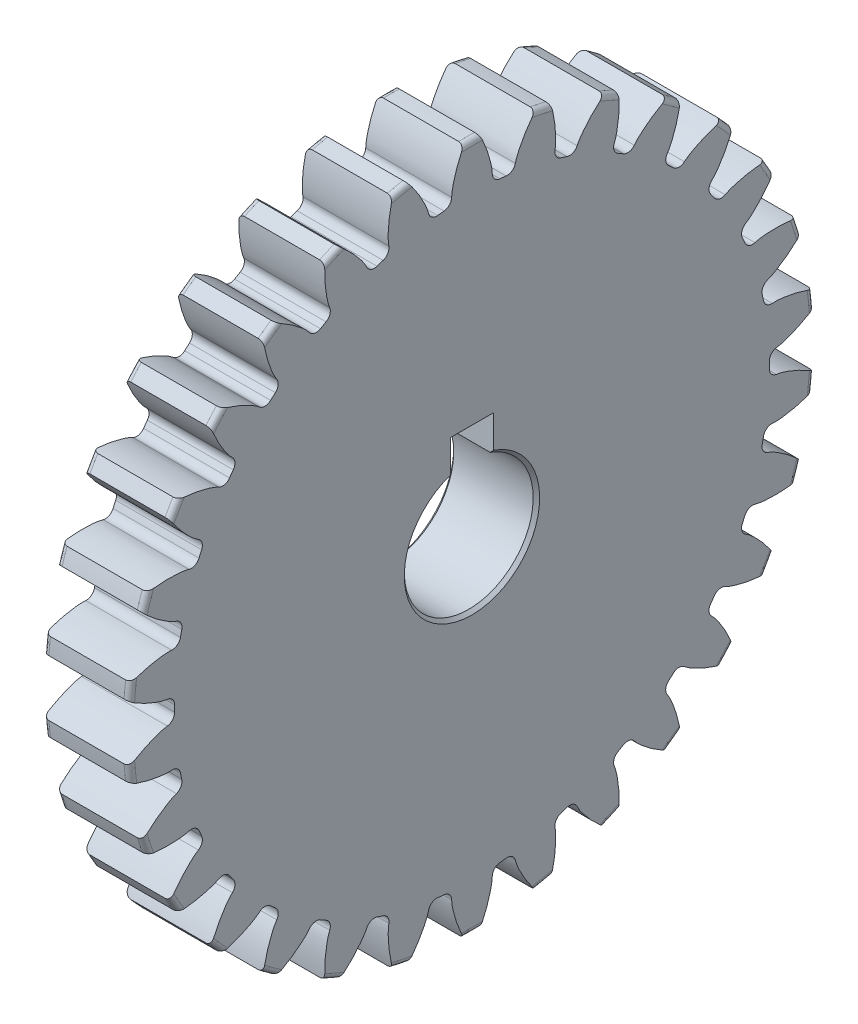
SolidWorks part; units mm, degrees
ref_plane "Front Plane" through (0, 0, 0) normal (0, 0, 1) x (1, 0, 0)
ref_plane "Top Plane" through (0, 0, 0) normal (0, 1, 0) x (1, 0, 0)
ref_plane "Right Plane" through (0, 0, 0) normal (1, 0, 0) x (0, 0, -1)
sketch "Sketch1" plane through (0, 0, 0) normal (0, 0, 1) x (1, 0, 0)
  line L0 (-4.5, 16) -> (-4.5, 0)
  line L1 (-4.5, 0) -> (4.5, 0)
  line L2 (4.5, 0) -> (4.5, 16)
  line L3 (4.5, 16) -> (-4.5, 16)
  line L4 (-4.5, 0) -> (4.5, 0) construction
revolve "Revolve1" add sketch "Sketch1" angle 360 about L4 reverse direction yes
sketch "Sketch2" plane through (-4.5, 0, 0) normal (-1, 0, 0) x (0, 0, 1)
  arc A0 (0.9541, 13.8101) -> (1.9381, 13.7067) centre (0, 0) cw
  arc A1 (2.9651, 15.7229) -> (0.3687, 15.9958) centre (0, 0) ccw
  spline S0 degree 3 poles (0.3687, 15.9958) (0.4111, 15.912) (0.4521, 15.8276) (0.4915, 15.7423) (0.5615, 15.5907) (0.6264, 15.4366) (0.6838, 15.2798) (0.7414, 15.123) (0.7918, 14.9633) (0.8344, 14.8018) (0.89, 14.5911) (0.9382, 14.3754) (0.9452, 14.1576) (0.949, 14.0418) (0.9511, 13.9259) (0.9541, 13.8101) knots -0.000282 -0.000282 -0.000282 -0.000282 0 0 0 0.000501 0.000501 0.000501 0.001002 0.001002 0.001002 0.001658 0.001658 0.001658 0.002003 0.002003 0.002003 0.002003
  spline S1 degree 3 poles (1.9381, 13.7067) (1.965, 13.8194) (1.9912, 13.9322) (2.019, 14.0447) (2.0592, 14.2078) (2.1235, 14.365) (2.1953, 14.5168) (2.2668, 14.6678) (2.3448, 14.8159) (2.4297, 14.9597) (2.5401, 15.1466) (2.6623, 15.3267) (2.7923, 15.5005) (2.8485, 15.5757) (2.9062, 15.6498) (2.9651, 15.7229) knots -0.000345 -0.000345 -0.000345 -0.000345 0 0 0 0.000504 0.000504 0.000504 0.001004 0.001004 0.001004 0.001654 0.001654 0.001654 0.001934 0.001934 0.001934 0.001934
extrude "Cut-Extrude1" cut sketch "Sketch2" against normal through all
sketch "Sketch3" plane through (-4.5, 0, 0) normal (-1, 0, 0) x (0, 0, 1)
  arc A0 (3.8045, 13.3099) -> (4.7455, 13.0042) centre (0, 0) cw
  arc A1 (6.1693, 14.7628) -> (3.6863, 15.5696) centre (0, 0) ccw
  spline S0 degree 3 poles (3.6863, 15.5696) (3.7104, 15.4788) (3.733, 15.3877) (3.7537, 15.2961) (3.7907, 15.1333) (3.8221, 14.969) (3.8457, 14.8037) (3.8694, 14.6384) (3.8856, 14.4717) (3.8937, 14.3049) (3.9042, 14.0872) (3.9065, 13.8662) (3.8681, 13.6517) (3.8477, 13.5376) (3.8257, 13.4239) (3.8045, 13.3099) knots -0.000282 -0.000282 -0.000282 -0.000282 0 0 0 0.000501 0.000501 0.000501 0.001002 0.001002 0.001002 0.001658 0.001658 0.001658 0.002003 0.002003 0.002003 0.002003
  spline S1 degree 3 poles (4.7455, 13.0042) (4.7953, 13.1088) (4.8444, 13.2138) (4.8949, 13.3181) (4.9682, 13.4692) (5.0637, 13.6096) (5.1656, 13.7432) (5.2668, 13.876) (5.374, 14.0046) (5.4869, 14.1276) (5.6337, 14.2875) (5.7907, 14.4382) (5.954, 14.5812) (6.0246, 14.6431) (6.0964, 14.7036) (6.1693, 14.7628) knots -0.000345 -0.000345 -0.000345 -0.000345 0 0 0 0.000504 0.000504 0.000504 0.001004 0.001004 0.001004 0.001654 0.001654 0.001654 0.001934 0.001934 0.001934 0.001934
extrude "Cut-Extrude2" cut sketch "Sketch3" against normal through all
sketch "Sketch4" plane through (-4.5, 0, 0) normal (-1, 0, 0) x (0, 0, 1)
  arc A0 (6.4886, 12.2281) -> (7.3455, 11.7334) centre (0, 0) cw
  arc A1 (9.1038, 13.1575) -> (6.8429, 14.4629) centre (0, 0) ccw
  spline S0 degree 3 poles (6.8429, 14.4629) (6.8476, 14.3691) (6.8507, 14.2753) (6.852, 14.1814) (6.8542, 14.0145) (6.8508, 13.8472) (6.8396, 13.6806) (6.8283, 13.514) (6.8095, 13.3476) (6.7827, 13.1828) (6.7478, 12.9677) (6.704, 12.751) (6.6219, 12.5492) (6.5782, 12.4418) (6.5331, 12.3351) (6.4886, 12.2281) knots -0.000282 -0.000282 -0.000282 -0.000282 0 0 0 0.000501 0.000501 0.000501 0.001002 0.001002 0.001002 0.001658 0.001658 0.001658 0.002003 0.002003 0.002003 0.002003
  spline S1 degree 3 poles (7.3455, 11.7334) (7.416, 11.8254) (7.4858, 11.9178) (7.5569, 12.0093) (7.66, 12.142) (7.7827, 12.2594) (7.9101, 12.3689) (8.0367, 12.4777) (8.1682, 12.5813) (8.3043, 12.6781) (8.4812, 12.8039) (8.6661, 12.9188) (8.8555, 13.0247) (8.9374, 13.0705) (9.0203, 13.1147) (9.1038, 13.1575) knots -0.000345 -0.000345 -0.000345 -0.000345 0 0 0 0.000504 0.000504 0.000504 0.001004 0.001004 0.001004 0.001654 0.001654 0.001654 0.001934 0.001934 0.001934 0.001934
extrude "Cut-Extrude3" cut sketch "Sketch4" against normal through all
sketch "Sketch5" plane through (-4.5, 0, 0) normal (-1, 0, 0) x (0, 0, 1)
  arc A0 (8.8892, 10.6118) -> (9.6245, 9.9498) centre (0, 0) cw
  arc A1 (11.6405, 10.9772) -> (9.7003, 12.7241) centre (0, 0) ccw
  spline S0 degree 3 poles (9.7003, 12.7241) (9.6854, 12.6315) (9.669, 12.539) (9.6507, 12.4469) (9.6182, 12.2831) (9.5801, 12.1203) (9.5345, 11.9597) (9.4888, 11.799) (9.4358, 11.6402) (9.3754, 11.4845) (9.2965, 11.2813) (9.2086, 11.0785) (9.0863, 10.8981) (9.0213, 10.8022) (8.9549, 10.7072) (8.8892, 10.6118) knots -0.000282 -0.000282 -0.000282 -0.000282 0 0 0 0.000501 0.000501 0.000501 0.001002 0.001002 0.001002 0.001658 0.001658 0.001658 0.002003 0.002003 0.002003 0.002003
  spline S1 degree 3 poles (9.6245, 9.9498) (9.7125, 10.0251) (9.8001, 10.101) (9.8887, 10.1757) (10.0171, 10.284) (10.1615, 10.3733) (10.3088, 10.454) (10.4554, 10.5341) (10.6055, 10.6081) (10.7588, 10.6745) (10.9579, 10.7608) (11.1627, 10.8347) (11.37, 10.8989) (11.4596, 10.9267) (11.5499, 10.9527) (11.6405, 10.9772) knots -0.000345 -0.000345 -0.000345 -0.000345 0 0 0 0.000504 0.000504 0.000504 0.001004 0.001004 0.001004 0.001654 0.001654 0.001654 0.001934 0.001934 0.001934 0.001934
extrude "Cut-Extrude4" cut sketch "Sketch5" against normal through all
sketch "Sketch6" plane through (-4.5, 0, 0) normal (-1, 0, 0) x (0, 0, 1)
  arc A0 (10.9013, 8.5317) -> (11.4829, 7.7313) centre (0, 0) cw
  arc A1 (13.6684, 8.3172) -> (12.1338, 10.4293) centre (0, 0) ccw
  spline S0 degree 3 poles (12.1338, 10.4293) (12.1, 10.3417) (12.0647, 10.2547) (12.0277, 10.1684) (11.9619, 10.015) (11.8907, 9.8636) (11.8127, 9.716) (11.7346, 9.5683) (11.6498, 9.424) (11.5582, 9.2843) (11.4389, 9.102) (11.3107, 8.9218) (11.1536, 8.7708) (11.0701, 8.6906) (10.9854, 8.6114) (10.9013, 8.5317) knots -0.000282 -0.000282 -0.000282 -0.000282 0 0 0 0.000501 0.000501 0.000501 0.001002 0.001002 0.001002 0.001658 0.001658 0.001658 0.002003 0.002003 0.002003 0.002003
  spline S1 degree 3 poles (11.4829, 7.7313) (11.5846, 7.7867) (11.6861, 7.8427) (11.7882, 7.8974) (11.9364, 7.9766) (12.0962, 8.034) (12.2571, 8.0822) (12.4171, 8.1301) (12.5793, 8.1712) (12.743, 8.2043) (12.9558, 8.2474) (13.1714, 8.2771) (13.3875, 8.2968) (13.481, 8.3053) (13.5747, 8.312) (13.6684, 8.3172) knots -0.000345 -0.000345 -0.000345 -0.000345 0 0 0 0.000504 0.000504 0.000504 0.001004 0.001004 0.001004 0.001654 0.001654 0.001654 0.001934 0.001934 0.001934 0.001934
extrude "Cut-Extrude5" cut sketch "Sketch6" against normal through all
sketch "Sketch7" plane through (-4.5, 0, 0) normal (-1, 0, 0) x (0, 0, 1)
  arc A0 (12.4369, 6.0788) -> (12.8394, 5.1749) centre (0, 0) cw
  arc A1 (15.0989, 5.2936) -> (14.0371, 7.6786) centre (0, 0) ccw
  spline S0 degree 3 poles (14.0371, 7.6786) (13.9858, 7.6) (13.9331, 7.5222) (13.879, 7.4455) (13.7827, 7.3091) (13.6816, 7.1758) (13.5746, 7.0477) (13.4675, 6.9195) (13.3545, 6.7959) (13.236, 6.6783) (13.0813, 6.5248) (12.9185, 6.3752) (12.7335, 6.2602) (12.635, 6.199) (12.5358, 6.1392) (12.4369, 6.0788) knots -0.000282 -0.000282 -0.000282 -0.000282 0 0 0 0.000501 0.000501 0.000501 0.001002 0.001002 0.001002 0.001658 0.001658 0.001658 0.002003 0.002003 0.002003 0.002003
  spline S1 degree 3 poles (12.8394, 5.1749) (12.9504, 5.2079) (13.0613, 5.2417) (13.1726, 5.2739) (13.3339, 5.3206) (13.5022, 5.3435) (13.6696, 5.3572) (13.8361, 5.3708) (14.0033, 5.3773) (14.1703, 5.3756) (14.3874, 5.3735) (14.6045, 5.3577) (14.82, 5.3321) (14.9132, 5.321) (15.0062, 5.3081) (15.0989, 5.2936) knots -0.000345 -0.000345 -0.000345 -0.000345 0 0 0 0.000504 0.000504 0.000504 0.001004 0.001004 0.001004 0.001654 0.001654 0.001654 0.001934 0.001934 0.001934 0.001934
extrude "Cut-Extrude6" cut sketch "Sketch7" against normal through all
sketch "Sketch8" plane through (-4.5, 0, 0) normal (-1, 0, 0) x (0, 0, 1)
  arc A0 (13.429, 3.3602) -> (13.6347, 2.3924) centre (0, 0) cw
  arc A1 (15.8696, 2.0387) -> (15.3268, 4.5923) centre (0, 0) ccw
  spline S0 degree 3 poles (15.3268, 4.5923) (15.2603, 4.5261) (15.1926, 4.461) (15.1237, 4.3972) (15.0012, 4.2838) (14.8746, 4.1745) (14.7433, 4.0713) (14.6119, 3.9682) (14.4757, 3.8709) (14.3352, 3.7804) (14.152, 3.6625) (13.9617, 3.55) (13.7568, 3.476) (13.6478, 3.4366) (13.5383, 3.3988) (13.429, 3.3602) knots -0.000282 -0.000282 -0.000282 -0.000282 0 0 0 0.000501 0.000501 0.000501 0.001002 0.001002 0.001002 0.001658 0.001658 0.001658 0.002003 0.002003 0.002003 0.002003
  spline S1 degree 3 poles (13.6347, 2.3924) (13.7502, 2.4016) (13.8657, 2.4115) (13.9812, 2.4199) (14.1488, 2.432) (14.3181, 2.4195) (14.4847, 2.3981) (14.6504, 2.3768) (14.8153, 2.3483) (14.9783, 2.312) (15.1902, 2.2648) (15.3993, 2.2042) (15.6047, 2.1343) (15.6936, 2.1041) (15.7819, 2.0721) (15.8696, 2.0387) knots -0.000345 -0.000345 -0.000345 -0.000345 0 0 0 0.000504 0.000504 0.000504 0.001004 0.001004 0.001004 0.001654 0.001654 0.001654 0.001934 0.001934 0.001934 0.001934
extrude "Cut-Extrude7" cut sketch "Sketch8" against normal through all
sketch "Sketch9" plane through (-4.5, 0, 0) normal (-1, 0, 0) x (0, 0, 1)
  arc A0 (13.8342, 0.4947) -> (13.8342, -0.4947) centre (0, 0) cw
  arc A1 (15.9467, -1.3054) -> (15.9467, 1.3054) centre (0, 0) ccw
  spline S0 degree 3 poles (15.9467, 1.3054) (15.8678, 1.2544) (15.7881, 1.2048) (15.7075, 1.1567) (15.564, 1.0713) (15.4175, 0.9906) (15.2676, 0.9171) (15.1176, 0.8435) (14.9641, 0.7766) (14.808, 0.7174) (14.6042, 0.6401) (14.3947, 0.5696) (14.1788, 0.5398) (14.0641, 0.524) (13.9491, 0.5097) (13.8342, 0.4947) knots -0.000282 -0.000282 -0.000282 -0.000282 0 0 0 0.000501 0.000501 0.000501 0.001002 0.001002 0.001002 0.001658 0.001658 0.001658 0.002003 0.002003 0.002003 0.002003
  spline S1 degree 3 poles (13.8342, -0.4947) (13.9491, -0.5097) (14.0641, -0.524) (14.1788, -0.5398) (14.3452, -0.5628) (14.5082, -0.6103) (14.6668, -0.6659) (14.8244, -0.7211) (14.9798, -0.7833) (15.1317, -0.8527) (15.3291, -0.9429) (15.521, -1.0457) (15.7075, -1.1567) (15.7881, -1.2048) (15.8678, -1.2544) (15.9467, -1.3054) knots -0.000345 -0.000345 -0.000345 -0.000345 0 0 0 0.000504 0.000504 0.000504 0.001004 0.001004 0.001004 0.001654 0.001654 0.001654 0.001934 0.001934 0.001934 0.001934
extrude "Cut-Extrude8" cut sketch "Sketch9" against normal through all
sketch "Sketch10" plane through (-4.5, 0, 0) normal (-1, 0, 0) x (0, 0, 1)
  arc A0 (13.6347, -2.3924) -> (13.429, -3.3602) centre (0, 0) cw
  arc A1 (15.3268, -4.5923) -> (15.8696, -2.0387) centre (0, 0) ccw
  spline S0 degree 3 poles (15.8696, -2.0387) (15.7819, -2.0721) (15.6936, -2.1041) (15.6047, -2.1343) (15.4466, -2.1881) (15.2865, -2.2365) (15.1246, -2.2773) (14.9626, -2.3181) (14.7986, -2.3516) (14.6335, -2.3771) (14.4182, -2.4103) (14.1986, -2.4357) (13.9812, -2.4199) (13.8657, -2.4115) (13.7502, -2.4016) (13.6347, -2.3924) knots -0.000282 -0.000282 -0.000282 -0.000282 0 0 0 0.000501 0.000501 0.000501 0.001002 0.001002 0.001002 0.001658 0.001658 0.001658 0.002003 0.002003 0.002003 0.002003
  spline S1 degree 3 poles (13.429, -3.3602) (13.5383, -3.3988) (13.6478, -3.4366) (13.7568, -3.476) (13.9148, -3.533) (14.0643, -3.6134) (14.2078, -3.7007) (14.3505, -3.7876) (14.4896, -3.8806) (14.6238, -3.9801) (14.7981, -4.1094) (14.9644, -4.2498) (15.1237, -4.3972) (15.1926, -4.461) (15.2603, -4.5261) (15.3268, -4.5923) knots -0.000345 -0.000345 -0.000345 -0.000345 0 0 0 0.000504 0.000504 0.000504 0.001004 0.001004 0.001004 0.001654 0.001654 0.001654 0.001934 0.001934 0.001934 0.001934
extrude "Cut-Extrude9" cut sketch "Sketch10" against normal through all
sketch "Sketch11" plane through (-4.5, 0, 0) normal (-1, 0, 0) x (0, 0, 1)
  arc A0 (12.8394, -5.1749) -> (12.4369, -6.0788) centre (0, 0) cw
  arc A1 (14.0371, -7.6786) -> (15.0989, -5.2936) centre (0, 0) ccw
  spline S0 degree 3 poles (15.0989, -5.2936) (15.0062, -5.3081) (14.9132, -5.321) (14.82, -5.3321) (14.6542, -5.3518) (14.4875, -5.3659) (14.3206, -5.3721) (14.1537, -5.3783) (13.9863, -5.377) (13.8195, -5.3676) (13.602, -5.3554) (13.3819, -5.3345) (13.1726, -5.2739) (13.0613, -5.2417) (12.9504, -5.2079) (12.8394, -5.1749) knots -0.000282 -0.000282 -0.000282 -0.000282 0 0 0 0.000501 0.000501 0.000501 0.001002 0.001002 0.001002 0.001658 0.001658 0.001658 0.002003 0.002003 0.002003 0.002003
  spline S1 degree 3 poles (12.4369, -6.0788) (12.5358, -6.1392) (12.635, -6.199) (12.7335, -6.2602) (12.8761, -6.3489) (13.0057, -6.4586) (13.1279, -6.5738) (13.2494, -6.6884) (13.3662, -6.8084) (13.4767, -6.9336) (13.6203, -7.0963) (13.7538, -7.2682) (13.879, -7.4455) (13.9331, -7.5222) (13.9858, -7.6) (14.0371, -7.6786) knots -0.000345 -0.000345 -0.000345 -0.000345 0 0 0 0.000504 0.000504 0.000504 0.001004 0.001004 0.001004 0.001654 0.001654 0.001654 0.001934 0.001934 0.001934 0.001934
extrude "Cut-Extrude10" cut sketch "Sketch11" against normal through all
sketch "Sketch12" plane through (-4.5, 0, 0) normal (-1, 0, 0) x (0, 0, 1)
  arc A0 (11.4829, -7.7313) -> (10.9013, -8.5317) centre (0, 0) cw
  arc A1 (12.1338, -10.4293) -> (13.6684, -8.3172) centre (0, 0) ccw
  spline S0 degree 3 poles (13.6684, -8.3172) (13.5747, -8.312) (13.481, -8.3053) (13.3875, -8.2968) (13.2212, -8.2816) (13.0553, -8.2607) (12.8908, -8.2321) (12.7262, -8.2035) (12.5627, -8.1674) (12.4015, -8.1235) (12.1913, -8.0663) (11.9804, -8.0002) (11.7882, -7.8974) (11.6861, -7.8427) (11.5846, -7.7867) (11.4829, -7.7313) knots -0.000282 -0.000282 -0.000282 -0.000282 0 0 0 0.000501 0.000501 0.000501 0.001002 0.001002 0.001002 0.001658 0.001658 0.001658 0.002003 0.002003 0.002003 0.002003
  spline S1 degree 3 poles (10.9013, -8.5317) (10.9854, -8.6114) (11.0701, -8.6906) (11.1536, -8.7708) (11.2747, -8.8872) (11.3787, -9.0215) (11.4743, -9.1596) (11.5693, -9.297) (11.6585, -9.4386) (11.7406, -9.5841) (11.8473, -9.7731) (11.9421, -9.969) (12.0277, -10.1684) (12.0647, -10.2547) (12.1, -10.3417) (12.1338, -10.4293) knots -0.000345 -0.000345 -0.000345 -0.000345 0 0 0 0.000504 0.000504 0.000504 0.001004 0.001004 0.001004 0.001654 0.001654 0.001654 0.001934 0.001934 0.001934 0.001934
extrude "Cut-Extrude11" cut sketch "Sketch12" against normal through all
sketch "Sketch13" plane through (-4.5, 0, 0) normal (-1, 0, 0) x (0, 0, 1)
  arc A0 (9.6245, -9.9498) -> (8.8892, -10.6118) centre (0, 0) cw
  arc A1 (9.7003, -12.7241) -> (11.6405, -10.9772) centre (0, 0) ccw
  spline S0 degree 3 poles (11.6405, -10.9772) (11.5499, -10.9527) (11.4596, -10.9267) (11.37, -10.8989) (11.2105, -10.8495) (11.0525, -10.7945) (10.8975, -10.7324) (10.7425, -10.6702) (10.5901, -10.6009) (10.4416, -10.5245) (10.2478, -10.4248) (10.0552, -10.3162) (9.8887, -10.1757) (9.8001, -10.101) (9.7125, -10.0251) (9.6245, -9.9498) knots -0.000282 -0.000282 -0.000282 -0.000282 0 0 0 0.000501 0.000501 0.000501 0.001002 0.001002 0.001002 0.001658 0.001658 0.001658 0.002003 0.002003 0.002003 0.002003
  spline S1 degree 3 poles (8.8892, -10.6118) (8.9549, -10.7072) (9.0213, -10.8022) (9.0863, -10.8981) (9.1806, -11.0372) (9.2544, -11.1901) (9.3191, -11.3451) (9.3835, -11.4992) (9.4414, -11.6563) (9.4914, -11.8156) (9.5564, -12.0227) (9.6085, -12.2341) (9.6507, -12.4469) (9.669, -12.539) (9.6854, -12.6315) (9.7003, -12.7241) knots -0.000345 -0.000345 -0.000345 -0.000345 0 0 0 0.000504 0.000504 0.000504 0.001004 0.001004 0.001004 0.001654 0.001654 0.001654 0.001934 0.001934 0.001934 0.001934
extrude "Cut-Extrude12" cut sketch "Sketch13" against normal through all
sketch "Sketch14" plane through (-4.5, 0, 0) normal (-1, 0, 0) x (0, 0, 1)
  arc A0 (7.3455, -11.7334) -> (6.4886, -12.2281) centre (0, 0) cw
  arc A1 (6.8429, -14.4629) -> (9.1038, -13.1575) centre (0, 0) ccw
  spline S0 degree 3 poles (9.1038, -13.1575) (9.0203, -13.1147) (8.9374, -13.0705) (8.8555, -13.0247) (8.7098, -12.9432) (8.5667, -12.8566) (8.428, -12.7636) (8.2893, -12.6705) (8.1546, -12.571) (8.0252, -12.4654) (7.8564, -12.3276) (7.6907, -12.1814) (7.5569, -12.0093) (7.4858, -11.9178) (7.416, -11.8254) (7.3455, -11.7334) knots -0.000282 -0.000282 -0.000282 -0.000282 0 0 0 0.000501 0.000501 0.000501 0.001002 0.001002 0.001002 0.001658 0.001658 0.001658 0.002003 0.002003 0.002003 0.002003
  spline S1 degree 3 poles (6.4886, -12.2281) (6.5331, -12.3351) (6.5782, -12.4418) (6.6219, -12.5492) (6.6852, -12.7047) (6.7256, -12.8697) (6.7567, -13.0347) (6.7877, -13.1989) (6.8116, -13.3645) (6.8274, -13.5308) (6.848, -13.7469) (6.8549, -13.9644) (6.852, -14.1814) (6.8507, -14.2753) (6.8476, -14.3691) (6.8429, -14.4629) knots -0.000345 -0.000345 -0.000345 -0.000345 0 0 0 0.000504 0.000504 0.000504 0.001004 0.001004 0.001004 0.001654 0.001654 0.001654 0.001934 0.001934 0.001934 0.001934
extrude "Cut-Extrude13" cut sketch "Sketch14" against normal through all
sketch "Sketch15" plane through (-4.5, 0, 0) normal (-1, 0, 0) x (0, 0, 1)
  arc A0 (4.7455, -13.0042) -> (3.8045, -13.3099) centre (0, 0) cw
  arc A1 (3.6863, -15.5696) -> (6.1693, -14.7628) centre (0, 0) ccw
  spline S0 degree 3 poles (6.1693, -14.7628) (6.0964, -14.7036) (6.0246, -14.6431) (5.954, -14.5812) (5.8284, -14.4712) (5.7064, -14.3568) (5.5901, -14.2369) (5.4738, -14.117) (5.3628, -13.9918) (5.2582, -13.8615) (5.1217, -13.6917) (4.9899, -13.5141) (4.8949, -13.3181) (4.8444, -13.2138) (4.7953, -13.1088) (4.7455, -13.0042) knots -0.000282 -0.000282 -0.000282 -0.000282 0 0 0 0.000501 0.000501 0.000501 0.001002 0.001002 0.001002 0.001658 0.001658 0.001658 0.002003 0.002003 0.002003 0.002003
  spline S1 degree 3 poles (3.8045, -13.3099) (3.8257, -13.4239) (3.8477, -13.5376) (3.8681, -13.6517) (3.8977, -13.8171) (3.9029, -13.9868) (3.899, -14.1547) (3.8951, -14.3217) (3.8841, -14.4887) (3.865, -14.6546) (3.8402, -14.8702) (3.8018, -15.0845) (3.7537, -15.2961) (3.733, -15.3877) (3.7104, -15.4788) (3.6863, -15.5696) knots -0.000345 -0.000345 -0.000345 -0.000345 0 0 0 0.000504 0.000504 0.000504 0.001004 0.001004 0.001004 0.001654 0.001654 0.001654 0.001934 0.001934 0.001934 0.001934
extrude "Cut-Extrude14" cut sketch "Sketch15" against normal through all
sketch "Sketch16" plane through (-4.5, 0, 0) normal (-1, 0, 0) x (0, 0, 1)
  arc A0 (1.9381, -13.7067) -> (0.9541, -13.8101) centre (0, 0) cw
  arc A1 (0.3687, -15.9958) -> (2.9651, -15.7229) centre (0, 0) ccw
  spline S0 degree 3 poles (2.9651, -15.7229) (2.9062, -15.6498) (2.8485, -15.5757) (2.7923, -15.5005) (2.6923, -15.3668) (2.5968, -15.2295) (2.5079, -15.0881) (2.4191, -14.9466) (2.3365, -14.801) (2.2613, -14.6519) (2.1631, -14.4573) (2.0712, -14.2563) (2.019, -14.0447) (1.9912, -13.9322) (1.965, -13.8194) (1.9381, -13.7067) knots -0.000282 -0.000282 -0.000282 -0.000282 0 0 0 0.000501 0.000501 0.000501 0.001002 0.001002 0.001002 0.001658 0.001658 0.001658 0.002003 0.002003 0.002003 0.002003
  spline S1 degree 3 poles (0.9541, -13.8101) (0.9511, -13.9259) (0.949, -14.0418) (0.9452, -14.1576) (0.9398, -14.3255) (0.9096, -14.4926) (0.8709, -14.656) (0.8324, -14.8186) (0.7868, -14.9796) (0.7337, -15.138) (0.6646, -15.3437) (0.5824, -15.5453) (0.4915, -15.7423) (0.4521, -15.8276) (0.4111, -15.912) (0.3687, -15.9958) knots -0.000345 -0.000345 -0.000345 -0.000345 0 0 0 0.000504 0.000504 0.000504 0.001004 0.001004 0.001004 0.001654 0.001654 0.001654 0.001934 0.001934 0.001934 0.001934
extrude "Cut-Extrude15" cut sketch "Sketch16" against normal through all
sketch "Sketch17" plane through (-4.5, 0, 0) normal (-1, 0, 0) x (0, 0, 1)
  arc A0 (-0.9541, -13.8101) -> (-1.9381, -13.7067) centre (0, 0) cw
  arc A1 (-2.9651, -15.7229) -> (-0.3687, -15.9958) centre (0, 0) ccw
  spline S0 degree 3 poles (-0.3687, -15.9958) (-0.4111, -15.912) (-0.4521, -15.8276) (-0.4915, -15.7423) (-0.5615, -15.5907) (-0.6264, -15.4366) (-0.6838, -15.2798) (-0.7414, -15.123) (-0.7918, -14.9633) (-0.8344, -14.8018) (-0.89, -14.5911) (-0.9382, -14.3754) (-0.9452, -14.1576) (-0.949, -14.0418) (-0.9511, -13.9259) (-0.9541, -13.8101) knots -0.000282 -0.000282 -0.000282 -0.000282 0 0 0 0.000501 0.000501 0.000501 0.001002 0.001002 0.001002 0.001658 0.001658 0.001658 0.002003 0.002003 0.002003 0.002003
  spline S1 degree 3 poles (-1.9381, -13.7067) (-1.965, -13.8194) (-1.9912, -13.9322) (-2.019, -14.0447) (-2.0592, -14.2078) (-2.1235, -14.365) (-2.1953, -14.5168) (-2.2668, -14.6678) (-2.3448, -14.8159) (-2.4297, -14.9597) (-2.5401, -15.1466) (-2.6623, -15.3267) (-2.7923, -15.5005) (-2.8485, -15.5757) (-2.9062, -15.6498) (-2.9651, -15.7229) knots -0.000345 -0.000345 -0.000345 -0.000345 0 0 0 0.000504 0.000504 0.000504 0.001004 0.001004 0.001004 0.001654 0.001654 0.001654 0.001934 0.001934 0.001934 0.001934
extrude "Cut-Extrude16" cut sketch "Sketch17" against normal through all
sketch "Sketch18" plane through (-4.5, 0, 0) normal (-1, 0, 0) x (0, 0, 1)
  arc A0 (-3.8045, -13.3099) -> (-4.7455, -13.0042) centre (0, 0) cw
  arc A1 (-6.1693, -14.7628) -> (-3.6863, -15.5696) centre (0, 0) ccw
  spline S0 degree 3 poles (-3.6863, -15.5696) (-3.7104, -15.4788) (-3.733, -15.3877) (-3.7537, -15.2961) (-3.7907, -15.1333) (-3.8221, -14.969) (-3.8457, -14.8037) (-3.8694, -14.6384) (-3.8856, -14.4717) (-3.8937, -14.3049) (-3.9042, -14.0872) (-3.9065, -13.8662) (-3.8681, -13.6517) (-3.8477, -13.5376) (-3.8257, -13.4239) (-3.8045, -13.3099) knots -0.000282 -0.000282 -0.000282 -0.000282 0 0 0 0.000501 0.000501 0.000501 0.001002 0.001002 0.001002 0.001658 0.001658 0.001658 0.002003 0.002003 0.002003 0.002003
  spline S1 degree 3 poles (-4.7455, -13.0042) (-4.7953, -13.1088) (-4.8444, -13.2138) (-4.8949, -13.3181) (-4.9682, -13.4692) (-5.0637, -13.6096) (-5.1656, -13.7432) (-5.2668, -13.876) (-5.374, -14.0046) (-5.4869, -14.1276) (-5.6337, -14.2875) (-5.7907, -14.4382) (-5.954, -14.5812) (-6.0246, -14.6431) (-6.0964, -14.7036) (-6.1693, -14.7628) knots -0.000345 -0.000345 -0.000345 -0.000345 0 0 0 0.000504 0.000504 0.000504 0.001004 0.001004 0.001004 0.001654 0.001654 0.001654 0.001934 0.001934 0.001934 0.001934
extrude "Cut-Extrude17" cut sketch "Sketch18" against normal through all
sketch "Sketch19" plane through (-4.5, 0, 0) normal (-1, 0, 0) x (0, 0, 1)
  arc A0 (-6.4886, -12.2281) -> (-7.3455, -11.7334) centre (0, 0) cw
  arc A1 (-9.1038, -13.1575) -> (-6.8429, -14.4629) centre (0, 0) ccw
  spline S0 degree 3 poles (-6.8429, -14.4629) (-6.8476, -14.3691) (-6.8507, -14.2753) (-6.852, -14.1814) (-6.8542, -14.0145) (-6.8508, -13.8472) (-6.8396, -13.6806) (-6.8283, -13.514) (-6.8095, -13.3476) (-6.7827, -13.1828) (-6.7478, -12.9677) (-6.704, -12.751) (-6.6219, -12.5492) (-6.5782, -12.4418) (-6.5331, -12.3351) (-6.4886, -12.2281) knots -0.000282 -0.000282 -0.000282 -0.000282 0 0 0 0.000501 0.000501 0.000501 0.001002 0.001002 0.001002 0.001658 0.001658 0.001658 0.002003 0.002003 0.002003 0.002003
  spline S1 degree 3 poles (-7.3455, -11.7334) (-7.416, -11.8254) (-7.4858, -11.9178) (-7.5569, -12.0093) (-7.66, -12.142) (-7.7827, -12.2594) (-7.9101, -12.3689) (-8.0367, -12.4777) (-8.1682, -12.5813) (-8.3043, -12.6781) (-8.4812, -12.8039) (-8.6661, -12.9188) (-8.8555, -13.0247) (-8.9374, -13.0705) (-9.0203, -13.1147) (-9.1038, -13.1575) knots -0.000345 -0.000345 -0.000345 -0.000345 0 0 0 0.000504 0.000504 0.000504 0.001004 0.001004 0.001004 0.001654 0.001654 0.001654 0.001934 0.001934 0.001934 0.001934
extrude "Cut-Extrude18" cut sketch "Sketch19" against normal through all
sketch "Sketch20" plane through (-4.5, 0, 0) normal (-1, 0, 0) x (0, 0, 1)
  arc A0 (-8.8892, -10.6118) -> (-9.6245, -9.9498) centre (0, 0) cw
  arc A1 (-11.6405, -10.9772) -> (-9.7003, -12.7241) centre (0, 0) ccw
  spline S0 degree 3 poles (-9.7003, -12.7241) (-9.6854, -12.6315) (-9.669, -12.539) (-9.6507, -12.4469) (-9.6182, -12.2831) (-9.5801, -12.1203) (-9.5345, -11.9597) (-9.4888, -11.799) (-9.4358, -11.6402) (-9.3754, -11.4845) (-9.2965, -11.2813) (-9.2086, -11.0785) (-9.0863, -10.8981) (-9.0213, -10.8022) (-8.9549, -10.7072) (-8.8892, -10.6118) knots -0.000282 -0.000282 -0.000282 -0.000282 0 0 0 0.000501 0.000501 0.000501 0.001002 0.001002 0.001002 0.001658 0.001658 0.001658 0.002003 0.002003 0.002003 0.002003
  spline S1 degree 3 poles (-9.6245, -9.9498) (-9.7125, -10.0251) (-9.8001, -10.101) (-9.8887, -10.1757) (-10.0171, -10.284) (-10.1615, -10.3733) (-10.3088, -10.454) (-10.4554, -10.5341) (-10.6055, -10.6081) (-10.7588, -10.6745) (-10.9579, -10.7608) (-11.1627, -10.8347) (-11.37, -10.8989) (-11.4596, -10.9267) (-11.5499, -10.9527) (-11.6405, -10.9772) knots -0.000345 -0.000345 -0.000345 -0.000345 0 0 0 0.000504 0.000504 0.000504 0.001004 0.001004 0.001004 0.001654 0.001654 0.001654 0.001934 0.001934 0.001934 0.001934
extrude "Cut-Extrude19" cut sketch "Sketch20" against normal through all
sketch "Sketch21" plane through (-4.5, 0, 0) normal (-1, 0, 0) x (0, 0, 1)
  arc A0 (-10.9013, -8.5317) -> (-11.4829, -7.7313) centre (0, 0) cw
  arc A1 (-13.6684, -8.3172) -> (-12.1338, -10.4293) centre (0, 0) ccw
  spline S0 degree 3 poles (-12.1338, -10.4293) (-12.1, -10.3417) (-12.0647, -10.2547) (-12.0277, -10.1684) (-11.9619, -10.015) (-11.8907, -9.8636) (-11.8127, -9.716) (-11.7346, -9.5683) (-11.6498, -9.424) (-11.5582, -9.2843) (-11.4389, -9.102) (-11.3107, -8.9218) (-11.1536, -8.7708) (-11.0701, -8.6906) (-10.9854, -8.6114) (-10.9013, -8.5317) knots -0.000282 -0.000282 -0.000282 -0.000282 0 0 0 0.000501 0.000501 0.000501 0.001002 0.001002 0.001002 0.001658 0.001658 0.001658 0.002003 0.002003 0.002003 0.002003
  spline S1 degree 3 poles (-11.4829, -7.7313) (-11.5846, -7.7867) (-11.6861, -7.8427) (-11.7882, -7.8974) (-11.9364, -7.9766) (-12.0962, -8.034) (-12.2571, -8.0822) (-12.4171, -8.1301) (-12.5793, -8.1712) (-12.743, -8.2043) (-12.9558, -8.2474) (-13.1714, -8.2771) (-13.3875, -8.2968) (-13.481, -8.3053) (-13.5747, -8.312) (-13.6684, -8.3172) knots -0.000345 -0.000345 -0.000345 -0.000345 0 0 0 0.000504 0.000504 0.000504 0.001004 0.001004 0.001004 0.001654 0.001654 0.001654 0.001934 0.001934 0.001934 0.001934
extrude "Cut-Extrude20" cut sketch "Sketch21" against normal through all
sketch "Sketch22" plane through (-4.5, 0, 0) normal (-1, 0, 0) x (0, 0, 1)
  arc A0 (-12.4369, -6.0788) -> (-12.8394, -5.1749) centre (0, 0) cw
  arc A1 (-15.0989, -5.2936) -> (-14.0371, -7.6786) centre (0, 0) ccw
  spline S0 degree 3 poles (-14.0371, -7.6786) (-13.9858, -7.6) (-13.9331, -7.5222) (-13.879, -7.4455) (-13.7827, -7.3091) (-13.6816, -7.1758) (-13.5746, -7.0477) (-13.4675, -6.9195) (-13.3545, -6.7959) (-13.236, -6.6783) (-13.0813, -6.5248) (-12.9185, -6.3752) (-12.7335, -6.2602) (-12.635, -6.199) (-12.5358, -6.1392) (-12.4369, -6.0788) knots -0.000282 -0.000282 -0.000282 -0.000282 0 0 0 0.000501 0.000501 0.000501 0.001002 0.001002 0.001002 0.001658 0.001658 0.001658 0.002003 0.002003 0.002003 0.002003
  spline S1 degree 3 poles (-12.8394, -5.1749) (-12.9504, -5.2079) (-13.0613, -5.2417) (-13.1726, -5.2739) (-13.3339, -5.3206) (-13.5022, -5.3435) (-13.6696, -5.3572) (-13.8361, -5.3708) (-14.0033, -5.3773) (-14.1703, -5.3756) (-14.3874, -5.3735) (-14.6045, -5.3577) (-14.82, -5.3321) (-14.9132, -5.321) (-15.0062, -5.3081) (-15.0989, -5.2936) knots -0.000345 -0.000345 -0.000345 -0.000345 0 0 0 0.000504 0.000504 0.000504 0.001004 0.001004 0.001004 0.001654 0.001654 0.001654 0.001934 0.001934 0.001934 0.001934
extrude "Cut-Extrude21" cut sketch "Sketch22" against normal through all
sketch "Sketch23" plane through (-4.5, 0, 0) normal (-1, 0, 0) x (0, 0, 1)
  arc A0 (-13.429, -3.3602) -> (-13.6347, -2.3924) centre (0, 0) cw
  arc A1 (-15.8696, -2.0387) -> (-15.3268, -4.5923) centre (0, 0) ccw
  spline S0 degree 3 poles (-15.3268, -4.5923) (-15.2603, -4.5261) (-15.1926, -4.461) (-15.1237, -4.3972) (-15.0012, -4.2838) (-14.8746, -4.1745) (-14.7433, -4.0713) (-14.6119, -3.9682) (-14.4757, -3.8709) (-14.3352, -3.7804) (-14.152, -3.6625) (-13.9617, -3.55) (-13.7568, -3.476) (-13.6478, -3.4366) (-13.5383, -3.3988) (-13.429, -3.3602) knots -0.000282 -0.000282 -0.000282 -0.000282 0 0 0 0.000501 0.000501 0.000501 0.001002 0.001002 0.001002 0.001658 0.001658 0.001658 0.002003 0.002003 0.002003 0.002003
  spline S1 degree 3 poles (-13.6347, -2.3924) (-13.7502, -2.4016) (-13.8657, -2.4115) (-13.9812, -2.4199) (-14.1488, -2.432) (-14.3181, -2.4195) (-14.4847, -2.3981) (-14.6504, -2.3768) (-14.8153, -2.3483) (-14.9783, -2.312) (-15.1902, -2.2648) (-15.3993, -2.2042) (-15.6047, -2.1343) (-15.6936, -2.1041) (-15.7819, -2.0721) (-15.8696, -2.0387) knots -0.000345 -0.000345 -0.000345 -0.000345 0 0 0 0.000504 0.000504 0.000504 0.001004 0.001004 0.001004 0.001654 0.001654 0.001654 0.001934 0.001934 0.001934 0.001934
extrude "Cut-Extrude22" cut sketch "Sketch23" against normal through all
sketch "Sketch24" plane through (-4.5, 0, 0) normal (-1, 0, 0) x (0, 0, 1)
  arc A0 (-15.9467, 1.3054) -> (-15.9467, -1.3054) centre (0, 0) ccw
  arc A1 (-13.8342, -0.4947) -> (-13.8342, 0.4947) centre (0, 0) cw
  spline S0 degree 3 poles (-15.9467, -1.3054) (-15.8678, -1.2544) (-15.7881, -1.2048) (-15.7075, -1.1567) (-15.564, -1.0713) (-15.4175, -0.9906) (-15.2676, -0.9171) (-15.1176, -0.8435) (-14.9641, -0.7766) (-14.808, -0.7174) (-14.6042, -0.6401) (-14.3947, -0.5696) (-14.1788, -0.5398) (-14.0641, -0.524) (-13.9491, -0.5097) (-13.8342, -0.4947) knots -0.000282 -0.000282 -0.000282 -0.000282 0 0 0 0.000501 0.000501 0.000501 0.001002 0.001002 0.001002 0.001658 0.001658 0.001658 0.002003 0.002003 0.002003 0.002003
  spline S1 degree 3 poles (-13.8342, 0.4947) (-13.9491, 0.5097) (-14.0641, 0.524) (-14.1788, 0.5398) (-14.3452, 0.5628) (-14.5082, 0.6103) (-14.6668, 0.6659) (-14.8244, 0.7211) (-14.9798, 0.7833) (-15.1317, 0.8527) (-15.3291, 0.9429) (-15.521, 1.0457) (-15.7075, 1.1567) (-15.7881, 1.2048) (-15.8678, 1.2544) (-15.9467, 1.3054) knots -0.000345 -0.000345 -0.000345 -0.000345 0 0 0 0.000504 0.000504 0.000504 0.001004 0.001004 0.001004 0.001654 0.001654 0.001654 0.001934 0.001934 0.001934 0.001934
extrude "Cut-Extrude23" cut sketch "Sketch24" against normal through all
sketch "Sketch25" plane through (-4.5, 0, 0) normal (-1, 0, 0) x (0, 0, 1)
  arc A0 (-15.3268, 4.5923) -> (-15.8696, 2.0387) centre (0, 0) ccw
  arc A1 (-13.6347, 2.3924) -> (-13.429, 3.3602) centre (0, 0) cw
  spline S0 degree 3 poles (-15.8696, 2.0387) (-15.7819, 2.0721) (-15.6936, 2.1041) (-15.6047, 2.1343) (-15.4466, 2.1881) (-15.2865, 2.2365) (-15.1246, 2.2773) (-14.9626, 2.3181) (-14.7986, 2.3516) (-14.6335, 2.3771) (-14.4182, 2.4103) (-14.1986, 2.4357) (-13.9812, 2.4199) (-13.8657, 2.4115) (-13.7502, 2.4016) (-13.6347, 2.3924) knots -0.000282 -0.000282 -0.000282 -0.000282 0 0 0 0.000501 0.000501 0.000501 0.001002 0.001002 0.001002 0.001658 0.001658 0.001658 0.002003 0.002003 0.002003 0.002003
  spline S1 degree 3 poles (-13.429, 3.3602) (-13.5383, 3.3988) (-13.6478, 3.4366) (-13.7568, 3.476) (-13.9148, 3.533) (-14.0643, 3.6134) (-14.2078, 3.7007) (-14.3505, 3.7876) (-14.4896, 3.8806) (-14.6238, 3.9801) (-14.7981, 4.1094) (-14.9644, 4.2498) (-15.1237, 4.3972) (-15.1926, 4.461) (-15.2603, 4.5261) (-15.3268, 4.5923) knots -0.000345 -0.000345 -0.000345 -0.000345 0 0 0 0.000504 0.000504 0.000504 0.001004 0.001004 0.001004 0.001654 0.001654 0.001654 0.001934 0.001934 0.001934 0.001934
extrude "Cut-Extrude24" cut sketch "Sketch25" against normal through all
sketch "Sketch26" plane through (-4.5, 0, 0) normal (-1, 0, 0) x (0, 0, 1)
  arc A0 (-14.0371, 7.6786) -> (-15.0989, 5.2936) centre (0, 0) ccw
  arc A1 (-12.8394, 5.1749) -> (-12.4369, 6.0788) centre (0, 0) cw
  spline S0 degree 3 poles (-15.0989, 5.2936) (-15.0062, 5.3081) (-14.9132, 5.321) (-14.82, 5.3321) (-14.6542, 5.3518) (-14.4875, 5.3659) (-14.3206, 5.3721) (-14.1537, 5.3783) (-13.9863, 5.377) (-13.8195, 5.3676) (-13.602, 5.3554) (-13.3819, 5.3345) (-13.1726, 5.2739) (-13.0613, 5.2417) (-12.9504, 5.2079) (-12.8394, 5.1749) knots -0.000282 -0.000282 -0.000282 -0.000282 0 0 0 0.000501 0.000501 0.000501 0.001002 0.001002 0.001002 0.001658 0.001658 0.001658 0.002003 0.002003 0.002003 0.002003
  spline S1 degree 3 poles (-12.4369, 6.0788) (-12.5358, 6.1392) (-12.635, 6.199) (-12.7335, 6.2602) (-12.8761, 6.3489) (-13.0057, 6.4586) (-13.1279, 6.5738) (-13.2494, 6.6884) (-13.3662, 6.8084) (-13.4767, 6.9336) (-13.6203, 7.0963) (-13.7538, 7.2682) (-13.879, 7.4455) (-13.9331, 7.5222) (-13.9858, 7.6) (-14.0371, 7.6786) knots -0.000345 -0.000345 -0.000345 -0.000345 0 0 0 0.000504 0.000504 0.000504 0.001004 0.001004 0.001004 0.001654 0.001654 0.001654 0.001934 0.001934 0.001934 0.001934
extrude "Cut-Extrude25" cut sketch "Sketch26" against normal through all
sketch "Sketch27" plane through (-4.5, 0, 0) normal (-1, 0, 0) x (0, 0, 1)
  arc A0 (-12.1338, 10.4293) -> (-13.6684, 8.3172) centre (0, 0) ccw
  arc A1 (-11.4829, 7.7313) -> (-10.9013, 8.5317) centre (0, 0) cw
  spline S0 degree 3 poles (-13.6684, 8.3172) (-13.5747, 8.312) (-13.481, 8.3053) (-13.3875, 8.2968) (-13.2212, 8.2816) (-13.0553, 8.2607) (-12.8908, 8.2321) (-12.7262, 8.2035) (-12.5627, 8.1674) (-12.4015, 8.1235) (-12.1913, 8.0663) (-11.9804, 8.0002) (-11.7882, 7.8974) (-11.6861, 7.8427) (-11.5846, 7.7867) (-11.4829, 7.7313) knots -0.000282 -0.000282 -0.000282 -0.000282 0 0 0 0.000501 0.000501 0.000501 0.001002 0.001002 0.001002 0.001658 0.001658 0.001658 0.002003 0.002003 0.002003 0.002003
  spline S1 degree 3 poles (-10.9013, 8.5317) (-10.9854, 8.6114) (-11.0701, 8.6906) (-11.1536, 8.7708) (-11.2747, 8.8872) (-11.3787, 9.0215) (-11.4743, 9.1596) (-11.5693, 9.297) (-11.6585, 9.4386) (-11.7406, 9.5841) (-11.8473, 9.7731) (-11.9421, 9.969) (-12.0277, 10.1684) (-12.0647, 10.2547) (-12.1, 10.3417) (-12.1338, 10.4293) knots -0.000345 -0.000345 -0.000345 -0.000345 0 0 0 0.000504 0.000504 0.000504 0.001004 0.001004 0.001004 0.001654 0.001654 0.001654 0.001934 0.001934 0.001934 0.001934
extrude "Cut-Extrude26" cut sketch "Sketch27" against normal through all
sketch "Sketch28" plane through (-4.5, 0, 0) normal (-1, 0, 0) x (0, 0, 1)
  arc A0 (-9.7003, 12.7241) -> (-11.6405, 10.9772) centre (0, 0) ccw
  arc A1 (-9.6245, 9.9498) -> (-8.8892, 10.6118) centre (0, 0) cw
  spline S0 degree 3 poles (-11.6405, 10.9772) (-11.5499, 10.9527) (-11.4596, 10.9267) (-11.37, 10.8989) (-11.2105, 10.8495) (-11.0525, 10.7945) (-10.8975, 10.7324) (-10.7425, 10.6702) (-10.5901, 10.6009) (-10.4416, 10.5245) (-10.2478, 10.4248) (-10.0552, 10.3162) (-9.8887, 10.1757) (-9.8001, 10.101) (-9.7125, 10.0251) (-9.6245, 9.9498) knots -0.000282 -0.000282 -0.000282 -0.000282 0 0 0 0.000501 0.000501 0.000501 0.001002 0.001002 0.001002 0.001658 0.001658 0.001658 0.002003 0.002003 0.002003 0.002003
  spline S1 degree 3 poles (-8.8892, 10.6118) (-8.9549, 10.7072) (-9.0213, 10.8022) (-9.0863, 10.8981) (-9.1806, 11.0372) (-9.2544, 11.1901) (-9.3191, 11.3451) (-9.3835, 11.4992) (-9.4414, 11.6563) (-9.4914, 11.8156) (-9.5564, 12.0227) (-9.6085, 12.2341) (-9.6507, 12.4469) (-9.669, 12.539) (-9.6854, 12.6315) (-9.7003, 12.7241) knots -0.000345 -0.000345 -0.000345 -0.000345 0 0 0 0.000504 0.000504 0.000504 0.001004 0.001004 0.001004 0.001654 0.001654 0.001654 0.001934 0.001934 0.001934 0.001934
extrude "Cut-Extrude27" cut sketch "Sketch28" against normal through all
sketch "Sketch29" plane through (-4.5, 0, 0) normal (-1, 0, 0) x (0, 0, 1)
  arc A0 (-6.8429, 14.4629) -> (-9.1038, 13.1575) centre (0, 0) ccw
  arc A1 (-7.3455, 11.7334) -> (-6.4886, 12.2281) centre (0, 0) cw
  spline S0 degree 3 poles (-9.1038, 13.1575) (-9.0203, 13.1147) (-8.9374, 13.0705) (-8.8555, 13.0247) (-8.7098, 12.9432) (-8.5667, 12.8566) (-8.428, 12.7636) (-8.2893, 12.6705) (-8.1546, 12.571) (-8.0252, 12.4654) (-7.8564, 12.3276) (-7.6907, 12.1814) (-7.5569, 12.0093) (-7.4858, 11.9178) (-7.416, 11.8254) (-7.3455, 11.7334) knots -0.000282 -0.000282 -0.000282 -0.000282 0 0 0 0.000501 0.000501 0.000501 0.001002 0.001002 0.001002 0.001658 0.001658 0.001658 0.002003 0.002003 0.002003 0.002003
  spline S1 degree 3 poles (-6.4886, 12.2281) (-6.5331, 12.3351) (-6.5782, 12.4418) (-6.6219, 12.5492) (-6.6852, 12.7047) (-6.7256, 12.8697) (-6.7567, 13.0347) (-6.7877, 13.1989) (-6.8116, 13.3645) (-6.8274, 13.5308) (-6.848, 13.7469) (-6.8549, 13.9644) (-6.852, 14.1814) (-6.8507, 14.2753) (-6.8476, 14.3691) (-6.8429, 14.4629) knots -0.000345 -0.000345 -0.000345 -0.000345 0 0 0 0.000504 0.000504 0.000504 0.001004 0.001004 0.001004 0.001654 0.001654 0.001654 0.001934 0.001934 0.001934 0.001934
extrude "Cut-Extrude28" cut sketch "Sketch29" against normal through all
sketch "Sketch30" plane through (-4.5, 0, 0) normal (-1, 0, 0) x (0, 0, 1)
  arc A0 (-3.6863, 15.5696) -> (-6.1693, 14.7628) centre (0, 0) ccw
  arc A1 (-4.7455, 13.0042) -> (-3.8045, 13.3099) centre (0, 0) cw
  spline S0 degree 3 poles (-6.1693, 14.7628) (-6.0964, 14.7036) (-6.0246, 14.6431) (-5.954, 14.5812) (-5.8284, 14.4712) (-5.7064, 14.3568) (-5.5901, 14.2369) (-5.4738, 14.117) (-5.3628, 13.9918) (-5.2582, 13.8615) (-5.1217, 13.6917) (-4.9899, 13.5141) (-4.8949, 13.3181) (-4.8444, 13.2138) (-4.7953, 13.1088) (-4.7455, 13.0042) knots -0.000282 -0.000282 -0.000282 -0.000282 0 0 0 0.000501 0.000501 0.000501 0.001002 0.001002 0.001002 0.001658 0.001658 0.001658 0.002003 0.002003 0.002003 0.002003
  spline S1 degree 3 poles (-3.8045, 13.3099) (-3.8257, 13.4239) (-3.8477, 13.5376) (-3.8681, 13.6517) (-3.8977, 13.8171) (-3.9029, 13.9868) (-3.899, 14.1547) (-3.8951, 14.3217) (-3.8841, 14.4887) (-3.865, 14.6546) (-3.8402, 14.8702) (-3.8018, 15.0845) (-3.7537, 15.2961) (-3.733, 15.3877) (-3.7104, 15.4788) (-3.6863, 15.5696) knots -0.000345 -0.000345 -0.000345 -0.000345 0 0 0 0.000504 0.000504 0.000504 0.001004 0.001004 0.001004 0.001654 0.001654 0.001654 0.001934 0.001934 0.001934 0.001934
extrude "Cut-Extrude29" cut sketch "Sketch30" against normal through all
sketch "Sketch31" plane through (-4.5, 0, 0) normal (-1, 0, 0) x (0, 0, 1)
  arc A0 (-0.3687, 15.9958) -> (-2.9651, 15.7229) centre (0, 0) ccw
  arc A1 (-1.9381, 13.7067) -> (-0.9541, 13.8101) centre (0, 0) cw
  spline S0 degree 3 poles (-2.9651, 15.7229) (-2.9062, 15.6498) (-2.8485, 15.5757) (-2.7923, 15.5005) (-2.6923, 15.3668) (-2.5968, 15.2295) (-2.5079, 15.0881) (-2.4191, 14.9466) (-2.3365, 14.801) (-2.2613, 14.6519) (-2.1631, 14.4573) (-2.0712, 14.2563) (-2.019, 14.0447) (-1.9912, 13.9322) (-1.965, 13.8194) (-1.9381, 13.7067) knots -0.000282 -0.000282 -0.000282 -0.000282 0 0 0 0.000501 0.000501 0.000501 0.001002 0.001002 0.001002 0.001658 0.001658 0.001658 0.002003 0.002003 0.002003 0.002003
  spline S1 degree 3 poles (-0.9541, 13.8101) (-0.9511, 13.9259) (-0.949, 14.0418) (-0.9452, 14.1576) (-0.9398, 14.3255) (-0.9096, 14.4926) (-0.8709, 14.656) (-0.8324, 14.8186) (-0.7868, 14.9796) (-0.7337, 15.138) (-0.6646, 15.3437) (-0.5824, 15.5453) (-0.4915, 15.7423) (-0.4521, 15.8276) (-0.4111, 15.912) (-0.3687, 15.9958) knots -0.000345 -0.000345 -0.000345 -0.000345 0 0 0 0.000504 0.000504 0.000504 0.001004 0.001004 0.001004 0.001654 0.001654 0.001654 0.001934 0.001934 0.001934 0.001934
extrude "Cut-Extrude30" cut sketch "Sketch31" against normal through all
ref_plane "Plane4" through (0, 0, 0) normal (0, 0, -1) x (-1, 0, 0)
fillet "Fillet2" radius 0.39 60 edges at (0, -0.4947, -13.8342) (0, 9.9498, -9.6245) (0, 5.1749, -12.8394) (0, -13.8101, 0.9541) (0, 13.0042, -4.7455) (0, -13.7067, 1.9381) (0, 2.3924, -13.6347) (0, -13.8101, -0.9541) (0, 7.7313, -11.4829) (0, -13.7067, -1.9381) (0, 11.7334, -7.3455) (0, -13.3099, 3.8045) (0, 13.8101, -0.9541) (0, -13.0042, 4.7455) (0, 2.3924, 13.6347) (0, -13.3099, -3.8045) (0, 5.1749, 12.8394) (0, -13.0042, -4.7455) (0, 7.7313, 11.4829) (0, -12.2281, 6.4886) (0, 9.9498, 9.6245) (0, -11.7334, 7.3455) (0, 11.7334, 7.3455) (0, -12.2281, -6.4886) (0, 13.0042, 4.7455) (0, -11.7334, -7.3455) (0, 13.7067, 1.9381) (0, -10.6118, 8.8892) (0, 0.4947, 13.8342) (0, -9.9498, 9.6245) (0, 0.4947, -13.8342) (0, -10.6118, -8.8892) (0, 3.3602, 13.429) (0, -9.9498, -9.6245) (0, 3.3602, -13.429) (0, -8.5317, 10.9013) (0, 6.0788, 12.4369) (0, -7.7313, 11.4829) (0, 6.0788, -12.4369) (0, -8.5317, -10.9013) (0, 8.5317, 10.9013) (0, -7.7313, -11.4829) (0, 8.5317, -10.9013) (0, -6.0788, 12.4369) (0, 10.6118, 8.8892) (0, -5.1749, 12.8394) (0, 10.6118, -8.8892) (0, -6.0788, -12.4369) (0, 12.2281, 6.4886) (0, -5.1749, -12.8394) (0, 12.2281, -6.4886) (0, -3.3602, 13.429) (0, 13.3099, 3.8045) (0, -2.3924, 13.6347) (0, 13.3099, -3.8045) (0, -3.3602, -13.429) (0, 13.8101, 0.9541) (0, -2.3924, -13.6347) (0, -0.4947, 13.8342) (0, 13.7067, -1.9381) tangent propagation no
sketch "Sketch40" plane through (0, 0, 0) normal (0, 1, 0) x (1, 0, 0)
  line L0 (-4.5, 15.0989) -> (-4.5, 13.1726) construction
  line L1 (-8.4464, 17.2217) -> (-2.5, 17.2217)
  line L2 (-8.4464, 17.2217) -> (-8.4464, -17.5419)
  line L3 (-8.4464, -17.5419) -> (-2.5, -17.5419)
  line L4 (-2.5, 17.2217) -> (-2.5, -17.5419)
  line L5 (2.5, -17.5419) -> (8.7666, -17.5419)
  line L6 (2.5, -17.5419) -> (2.5, 17.2217)
  line L7 (2.5, 17.2217) -> (8.7666, 17.2217)
  line L8 (8.7666, -17.5419) -> (8.7666, 17.2217)
  line L9 (4.5, 13.1726) -> (4.5, 15.0989) construction
  dimension "D1" = 2
  dimension "D2" = 2
extrude "Cut-Extrude31" cut sketch "Sketch40" against normal mid plane 40
hole_wizard "Ø4.0 (4) Diameter Hole1" positions "Sketch42" profile "Sketch41" hole size "Ø4.0" standard "ANSI Metric" end condition through all
sketch "Sketch42" plane through (-2.5, 0, 0) normal (-1, 0, 0) x (0, 0, 1)
  point P0 (0, 0)
sketch "Sketch41" plane through (-2.5, 0, 0) normal (0, 1, 0) x (0, 0, 1)
  line L0 (0, 0) -> (0, 5)
  line L1 (0, 5) -> (3, 5)
  line L2 (3, 5) -> (3, 0)
  line L5 (3, 0) -> (0, 0)
  line L11 (0, -6.35) -> (0, 107.95) construction
  dimension "Thru Hole Dia." = 6
  dimension "Thru Hole Depth" = 5
sketch "Sketch43" plane through (2.5, 0, 0) normal (1, 0, 0) x (0, 0, -1)
  line L0 (-1, 2.8284) -> (-1, 4.5)
  line L1 (-1, 4.5) -> (1, 4.5)
  line L2 (1, 4.5) -> (1, 2.8284)
  arc A0 (1, 2.8284) -> (-1, 2.8284) centre (0, 0) ccw
  dimension "D1" = 2
extrude "Cut-Extrude32" cut sketch "Sketch43" against normal through all
sketch "Sketch44" plane through (0, 0, 0) normal (0, 1, 0) x (1, 0, 0)
  line L0 (-2.5, 15.0989) -> (-2.5, 13.1726) construction
  line L1 (-4.2364, 16.7956) -> (-2, 16.7956)
  line L2 (-4.2364, 16.7956) -> (-4.2364, -16.7509)
  line L3 (-4.2364, -16.7509) -> (-2, -16.7509)
  line L4 (-2, 16.7956) -> (-2, -16.7509)
  line L5 (2, 16.7956) -> (6.2045, 16.7956)
  line L6 (2, 16.7956) -> (2, -16.7509)
  line L7 (2, -16.7509) -> (6.2045, -16.7509)
  line L8 (6.2045, 16.7956) -> (6.2045, -16.7509)
  line L9 (2.5, 13.1726) -> (2.5, 15.0989) construction
  dimension "D1" = 0.5
  dimension "D2" = 0.5
extrude "Cut-Extrude33" cut sketch "Sketch44" against normal mid plane 100
chamfer "Chamfer1" distance 0.15 angle 45 2 edges at (2, -3, 0) (-2, -3, 0)
fillet "Fillet3" radius 0.25 60 edges at (-2, 15.6504, -3.3266) (-2, 16, 0) (-2, 15.6504, 3.3266) (-2, 14.6167, 6.5078) (-2, 12.9443, 9.4046) (-2, 10.7061, 11.8903) (-2, 8, 13.8564) (-2, 4.9443, 15.2169) (-2, 1.6725, 15.9124) (-2, -1.6725, 15.9124) (-2, -4.9443, 15.2169) (-2, -8, 13.8564) (-2, -10.7061, 11.8903) (-2, -12.9443, 9.4046) (-2, -14.6167, 6.5078) (-2, -15.6504, 3.3266) (-2, -16, 0) (-2, -15.6504, -3.3266) (-2, -14.6167, -6.5078) (-2, -12.9443, -9.4046) (-2, -10.7061, -11.8903) (-2, -8, -13.8564) (-2, -4.9443, -15.2169) (-2, -1.6725, -15.9124) (-2, 1.6725, -15.9124) (-2, 4.9443, -15.2169) (-2, 8, -13.8564) (-2, 10.7061, -11.8903) (-2, 12.9443, -9.4046) (-2, 14.6167, -6.5078) (2, 10.7061, -11.8903) (2, 12.9443, -9.4046) (2, 14.6167, -6.5078) (2, 15.6504, -3.3266) (2, 16, 0) (2, 15.6504, 3.3266) (2, 14.6167, 6.5078) (2, 12.9443, 9.4046) (2, 10.7061, 11.8903) (2, 8, 13.8564) (2, 4.9443, 15.2169) (2, 1.6725, 15.9124) (2, -1.6725, 15.9124) (2, -4.9443, 15.2169) (2, -8, 13.8564) (2, -10.7061, 11.8903) (2, -12.9443, 9.4046) (2, -14.6167, 6.5078) (2, -15.6504, 3.3266) (2, -16, 0) (2, -15.6504, -3.3266) (2, -14.6167, -6.5078) (2, -12.9443, -9.4046) (2, -10.7061, -11.8903) (2, -8, -13.8564) (2, -4.9443, -15.2169) (2, -1.6725, -15.9124) (2, 1.6725, -15.9124) (2, 4.9443, -15.2169) (2, 8, -13.8564)
